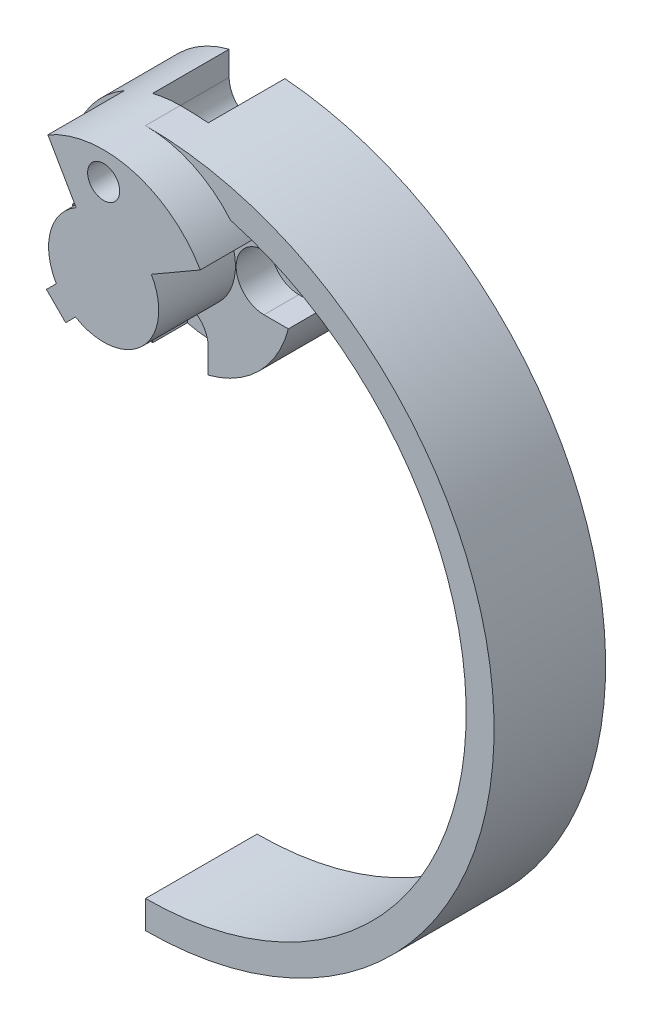
SolidWorks part; units mm, degrees
ref_plane "Front Plane" through (0, 0, 0) normal (0, 0, 1) x (1, 0, 0)
ref_plane "Top Plane" through (0, 0, 0) normal (0, 1, 0) x (1, 0, 0)
ref_plane "Right Plane" through (0, 0, 0) normal (1, 0, 0) x (0, 0, -1)
sketch "Leg-Sketch" plane through (0, 0, 0) normal (0, 0, 1) x (1, 0, 0)
  line L0 (0, 0) -> (0, -42) construction
  line L1 (0, -42) -> (0, -40)
  circle A0 centre (0, 0) radius 8 construction
  circle A1 centre (0, 0) radius 6 construction
  circle A2 centre (0, 6) radius 1.15
  circle A3 centre (-6, 0) radius 1.15
  circle A4 centre (0, -6) radius 1.15
  circle A5 centre (6, 0) radius 1.15
  arc A6 (0, 8) -> (0, -8) centre (0, 0) ccw
  arc A7 (0, 8) -> (0, -42) centre (0, -17) cw
  arc A8 (6.0995, 5.1765) -> (0, -40) centre (0, -17) cw
  arc A9 (0, -8) -> (6.0995, 5.1765) centre (0, 0) ccw
  point P12 (0, 8)
  dimension "D1" = 16
  dimension "D2" = 12
  dimension "D3" = 2.3
  dimension "D4" = 2
  dimension "D5" = 50
extrude "Leg" add sketch "Leg-Sketch" along normal blind 8
sketch "Hub-Sketch" plane through (0, 0, 0) normal (0, 0, -1) x (-1, 0, 0)
  circle A0 centre (0, 0) radius 8
  circle A1 centre (0, 6) radius 1.15 construction
  circle A2 centre (-6, 0) radius 1.15 construction
  circle A3 centre (0, -6) radius 1.15 construction
  circle A4 centre (6, 0) radius 1.15 construction
  circle A5 centre (0, 6) radius 1.15
  circle A6 centre (-6, 0) radius 1.15
  circle A7 centre (0, -6) radius 1.15
  circle A8 centre (6, 0) radius 1.15
extrude "Hub" add sketch "Hub-Sketch" along normal blind 3
sketch "Clearance-Sketch" plane through (0, 0, 8) normal (0, 0, 1) x (1, 0, 0)
  line L0 (6, 2) -> (8, 2)
  line L1 (8, 2) -> (8, -2)
  line L2 (8, -2) -> (6, -2)
  line L3 (2, -6) -> (2, -8)
  line L4 (2, -8) -> (-2, -8)
  line L5 (-2, -8) -> (-2, -6)
  line L6 (-6, -2) -> (-8, -2)
  line L7 (-8, -2) -> (-8, 2)
  line L8 (-8, 2) -> (-6, 2)
  line L9 (-2, 6) -> (-2, 8)
  line L10 (-2, 8) -> (2, 8)
  line L11 (2, 8) -> (2, 6)
  circle A0 centre (6, 0) radius 2 construction
  circle A1 centre (0, 6) radius 2 construction
  circle A2 centre (-6, 0) radius 2 construction
  circle A3 centre (0, -6) radius 2 construction
  arc A4 (2, 6) -> (-2, 6) centre (0, 6) cw
  arc A5 (-6, 2) -> (-6, -2) centre (-6, 0) cw
  arc A6 (-2, -6) -> (2, -6) centre (0, -6) cw
  arc A7 (6, -2) -> (6, 2) centre (6, 0) cw
  circle A8 centre (0, 0) radius 8 construction
  dimension "D1" = 4
extrude "Clearance" cut sketch "Clearance-Sketch" against normal offset from surface (5.5 mm away) 5.5 up to face at (-1.15, -6, -3)
sketch "Hub-Cutout-Sketch" plane through (0, 0, -3) normal (0, 0, -1) x (-1, 0, 0)
  line L0 (-3.4208, 1.975) -> (-6.9282, 4)
  line L1 (4, 6.9282) -> (1.975, 3.4208)
  line L7 (2.0172, -3.3961) -> (2.7243, -4.1032)
  line L8 (2.7243, -4.1032) -> (4.1032, -2.7243)
  line L9 (4.1032, -2.7243) -> (3.3961, -2.0172)
  line L10 (0, 0) -> (2.3478, 0) construction
  circle A1 centre (0, 0) radius 8 construction
  arc A2 (-6.9282, 4) -> (4, 6.9282) centre (0, 0) ccw
  arc A3 (-3.4208, 1.975) -> (2.0172, -3.3961) centre (0, 0) ccw
  arc A4 (3.3961, -2.0172) -> (1.975, 3.4208) centre (0, 0) ccw
  dimension "D2" = 3.95
  dimension "D1" = 90
  dimension "D3" = 45
  dimension "D4" = 1
  dimension "D5" = 1.95
  dimension "D6" = 30
extrude "Hub-Cutout" cut sketch "Hub-Cutout-Sketch" against normal up to surface (5.5 mm away) up to face at (4.85, 0, 2.5)
sketch "Cover-Bolts-Sketch" plane through (0, 0, 8) normal (0, 0, 1) x (1, 0, 0)
  line L0 (5.6569, 5.6569) -> (0, 0)
  line L1 (0, 0) -> (-5.6569, 5.6569)
  arc A0 (-5.6569, 5.6569) -> (5.6569, 5.6569) centre (0, 0) ccw
  arc A1 (-2, 7.746) -> (-7.746, 2) centre (0, 0) ccw construction
extrude "Cover-Bolts" add sketch "Cover-Bolts-Sketch" against normal offset from surface (3 mm away) 2.5 up to face at (-0.3679, -1.2187, 2.5)
mirror "Mirror" about plane through (0, 0, 0) normal (0, 0, 1) of bodies 106
delete or keep bodies "KeepMirrorBody" type keep bodies bodies 108
equation "\"D1@Hub\" = \"HUB_WIDTH\""
equation "\"LEG_CLEARANCE\"= 3mm"
equation "\"LEG_WIDTH\"= 8mm"
equation "\"LEG_THICKNESS\"= 2mm"
equation "\"LEG_DIAMETER\"= 50mm"
equation "\"HUB_WIDTH\"= \"LEG_CLEARANCE\""
equation "\"D5@Leg-Sketch\" = \"LEG_DIAMETER\""
equation "\"D4@Leg-Sketch\" = \"LEG_THICKNESS\""
equation "\"D1@Leg\"=\"LEG_WIDTH\""
